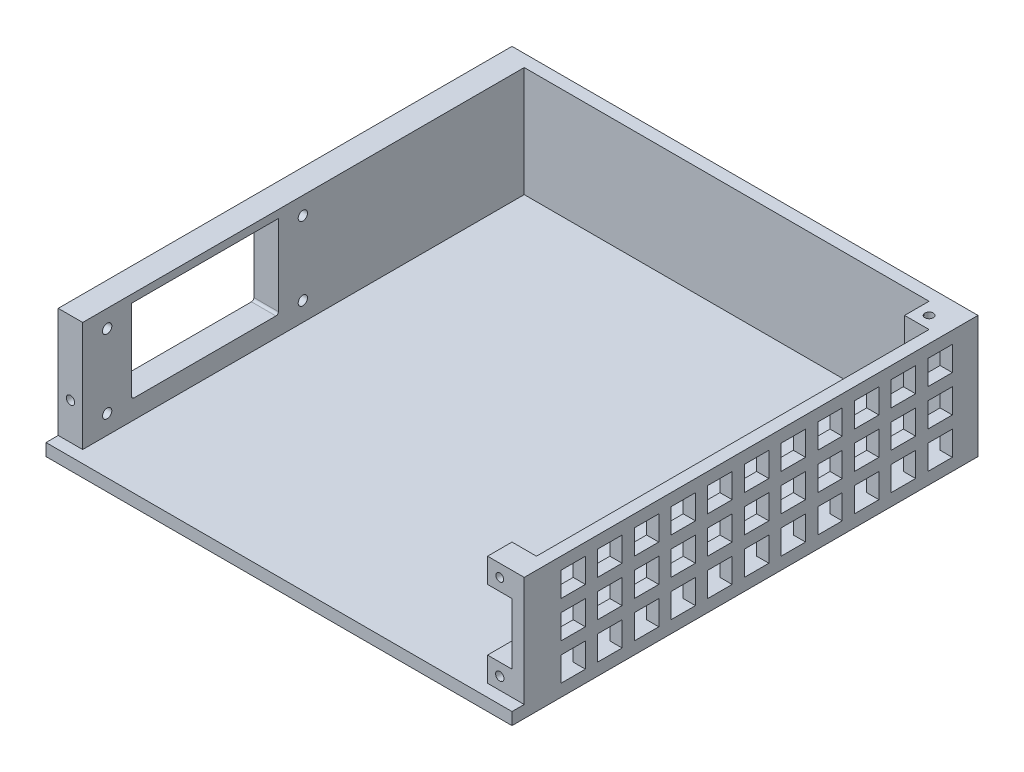
SolidWorks part; units mm, degrees
ref_plane "Front Plane" through (0, 0, 0) normal (0, 0, 1) x (1, 0, 0)
ref_plane "Top Plane" through (0, 0, 0) normal (0, 1, 0) x (1, 0, 0)
ref_plane "Right Plane" through (0, 0, 0) normal (1, 0, 0) x (0, 0, -1)
sketch "Sketch1" plane through (0, 0, 0) normal (0, 1, 0) x (1, 0, 0)
  line L1 (-95.25, 95.25) -> (95.25, 95.25)
  line L2 (-95.25, 95.25) -> (-95.25, -95.25)
  line L3 (-95.25, -95.25) -> (95.25, -95.25)
  line L4 (95.25, 95.25) -> (95.25, -95.25)
  line L5 (-95.25, 95.25) -> (95.25, -95.25) construction
  line L6 (-95.25, -95.25) -> (95.25, 95.25) construction
  point P0 (0, 0)
  dimension "D1" = 190.5
  dimension "D2" = 190.5
extrude "Boss-Extrude1" add sketch "Sketch1" along normal blind 5
sketch "Sketch9" plane through (0, 5, 0) normal (0, 1, 0) x (1, 0, 0)
  line L0 (95.25, -95.25) -> (95.25, 95.25) construction
  line L1 (-95.25, 95.25) -> (95.25, 95.25)
  line L2 (-95.25, 95.25) -> (-95.25, 90.25)
  line L3 (-95.25, 90.25) -> (95.25, 90.25)
  line L4 (95.25, 95.25) -> (95.25, 90.25)
  dimension "D1" = 5
extrude "Boss-Extrude5" add sketch "Sketch9" along normal blind 45
sketch "Sketch10" plane through (0, 5, 0) normal (0, 1, 0) x (1, 0, 0)
  line L0 (-95.25, -95.25) -> (95.25, -95.25) construction
  line L1 (95.25, 90.25) -> (90.25, 90.25)
  line L2 (95.25, 90.25) -> (95.25, -95.25)
  line L3 (95.25, -95.25) -> (90.25, -95.25)
  line L4 (90.25, 90.25) -> (90.25, -95.25)
  dimension "D1" = 5
extrude "Boss-Extrude6" add sketch "Sketch10" along normal up to surface (45 mm away) up to face at (0, 50, -92.75)
sketch "Sketch11" plane through (95.25, 0, 0) normal (1, 0, 0) x (0, 0, -1)
  line L0 (-95.25, 50) -> (95.25, 50) construction
  line L1 (-65.25, 45) -> (-75.25, 45)
  line L2 (-65.25, 45) -> (-65.25, 35)
  line L3 (-65.25, 35) -> (-75.25, 35)
  line L4 (-75.25, 45) -> (-75.25, 35)
  line L5 (-95.25, 50) -> (-95.25, 0) construction
  dimension "D1" = 5
  dimension "D2" = 20
  dimension "D3" = 10
  dimension "D4" = 10
extrude "Cut-Extrude3" cut sketch "Sketch11" against normal up to surface (5 mm away) up to face at (90.25, 27.5, 2.5)
pattern_linear "LPattern3" count 3 spacing 15 along (0, -1, 0) of "Cut-Extrude3"
pattern_linear "LPattern4" count 11 spacing 15 along (0, 0, -1) of "LPattern3"
sketch "Sketch12" plane through (-95.25, 0, 0) normal (-1, 0, 0) x (0, 0, 1)
  line L1 (-90.25, 5) -> (-80.25, 5)
  line L2 (-90.25, 5) -> (-90.25, 15)
  line L3 (-90.25, 15) -> (-80.25, 15)
  line L4 (-80.25, 5) -> (-80.25, 15)
  dimension "D1" = 10
  dimension "D2" = 10
extrude "Boss-Extrude7" add sketch "Sketch12" against normal blind 10
mirror "Mirror1" about plane through (0, 0, 0) normal (0, 0, 1) of "Boss-Extrude7"
sketch "Sketch13" plane through (0, 50, 0) normal (0, 1, 0) x (1, 0, 0)
  line L0 (90.25, 90.25) -> (90.25, -95.25) construction
  line L1 (95.25, -95.25) -> (90.25, -95.25)
  line L2 (95.25, -95.25) -> (95.25, -90.25)
  line L3 (95.25, -90.25) -> (90.25, -90.25)
  line L4 (90.25, -95.25) -> (90.25, -90.25)
  dimension "D1" = 5
extrude "Cut-Extrude4" cut sketch "Sketch13" against normal up to surface (45 mm away) up to face at (65.5463, 5, -0.3426)
sketch "Sketch15" plane through (0, 0, -90.25) normal (0, 0, 1) x (1, 0, 0)
  line L1 (-95.25, 50) -> (-85.25, 50)
  line L2 (-95.25, 50) -> (-95.25, 40)
  line L3 (-95.25, 40) -> (-85.25, 40)
  line L4 (-85.25, 50) -> (-85.25, 40)
  line L5 (90.25, 50) -> (80.25, 50)
  line L6 (90.25, 50) -> (90.25, 40)
  line L7 (90.25, 40) -> (80.25, 40)
  line L8 (80.25, 50) -> (80.25, 40)
  dimension "D1" = 10
  dimension "D2" = 10
extrude "Boss-Extrude8" add sketch "Sketch15" along normal blind 10
sketch "Sketch17" plane through (0, 50, 0) normal (0, 1, 0) x (1, 0, 0)
  line L1 (80.25, 80.25) -> (80.25, 90.25) construction
  line L2 (90.25, 80.25) -> (80.25, 80.25) construction
  circle A0 centre (85.25, 85.25) radius 1.7
  dimension "D1" = 3.4
  dimension "D2" = 5
  dimension "D3" = 5
extrude "Cut-Extrude7" cut sketch "Sketch17" against normal up to surface (10 mm away) up to face at (86.25, 40, -85.15)
sketch "Sketch18" plane through (90.25, 0, 0) normal (-1, 0, 0) x (0, 0, 1)
  line L1 (90.25, 50) -> (80.25, 50)
  line L2 (90.25, 50) -> (90.25, 40)
  line L3 (90.25, 40) -> (80.25, 40)
  line L4 (80.25, 50) -> (80.25, 40)
  dimension "D1" = 10
  dimension "D2" = 10
extrude "Boss-Extrude9" add sketch "Sketch18" along normal blind 10
sketch "Sketch19" plane through (0, 0, 90.25) normal (0, 0, 1) x (1, 0, 0)
  line L0 (80.25, 40) -> (80.25, 50) construction
  line L1 (80.25, 40) -> (90.25, 40) construction
  circle A0 centre (85.25, 45) radius 1.6
  dimension "D1" = 5
  dimension "D2" = 3.2
  dimension "D3" = 5
extrude "Cut-Extrude8" cut sketch "Sketch19" against normal up to surface (10 mm away) up to face at (85.25, 45, 80.25)
sketch "Sketch20" plane through (0, 0, 90.25) normal (0, 0, 1) x (1, 0, 0)
  line L1 (-85.25, 15) -> (-95.25, 15)
  line L2 (-85.25, 15) -> (-85.25, 25)
  line L3 (-85.25, 25) -> (-95.25, 25)
  line L4 (-95.25, 15) -> (-95.25, 25)
  dimension "D1" = 10
  dimension "D2" = 10
extrude "Boss-Extrude10" add sketch "Sketch20" against normal up to surface (10 mm away) up to face at (-90.25, 10, 80.25)
sketch "Sketch22" plane through (90.25, 0, 0) normal (-1, 0, 0) x (0, 0, 1)
  line L1 (90.25, 5) -> (80.25, 5)
  line L2 (90.25, 5) -> (90.25, 15)
  line L3 (90.25, 15) -> (80.25, 15)
  line L4 (80.25, 5) -> (80.25, 15)
  dimension "D1" = 10
  dimension "D2" = 10
extrude "Boss-Extrude11" add sketch "Sketch22" along normal blind 10
sketch "Sketch23" plane through (0, 0, 90.25) normal (0, 0, 1) x (1, 0, 0)
  line L0 (80.25, 5) -> (80.25, 15) construction
  line L1 (80.25, 15) -> (90.25, 15) construction
  circle A0 centre (85.25, 10) radius 1.7
  dimension "D1" = 3.4
  dimension "D2" = 5
  dimension "D3" = 5
extrude "Cut-Extrude10" cut sketch "Sketch23" against normal up to surface (10 mm away) up to face at (85.25, 10, 80.25)
sketch "Sketch24" plane through (-95.25, 0, 0) normal (-1, 0, 0) x (0, 0, 1)
  line L0 (-80.25, 50) -> (-80.25, 40)
  line L1 (-80.25, 50) -> (-80.25, 40) construction
  line L2 (-80.25, 40) -> (-90.25, 40)
  line L3 (-90.25, 40) -> (-90.25, 15)
  line L4 (-90.25, 15) -> (-80.25, 15)
  line L5 (-80.25, 15) -> (-80.25, 5)
  line L6 (-80.25, 5) -> (80.25, 5)
  line L7 (80.25, 5) -> (80.25, 25)
  line L8 (80.25, 25) -> (90.25, 25)
  line L9 (90.25, 25) -> (90.25, 50)
  line L10 (90.25, 50) -> (-80.25, 50)
extrude "Boss-Extrude12" add sketch "Sketch24" against normal up to surface (10 mm away) up to face at (-85.25, 45, -85.25)
sketch "Sketch25" plane through (-95.25, 0, 0) normal (-1, 0, 0) x (0, 0, 1)
  line L3 (10.25, 46.8) -> (10.25, 13.8)
  line L4 (11.25, 12.8) -> (69.25, 12.8)
  line L5 (70.25, 13.8) -> (70.25, 46.8)
  line L6 (0.25, 42.8) -> (80.25, 42.8) construction
  line L7 (80.25, 42.8) -> (80.25, 12.8) construction
  line L8 (80.25, 12.8) -> (0.25, 12.8) construction
  line L9 (0.25, 12.8) -> (0.25, 42.8) construction
  line L10 (10.25, 46.8) -> (70.25, 46.8)
  line L11 (-95.25, 0) -> (95.25, 0) construction
  line L12 (90.25, 50) -> (90.25, 5) construction
  arc A6 (10.25, 13.8) -> (11.25, 12.8) centre (11.25, 13.8) ccw
  arc A7 (69.25, 12.8) -> (70.25, 13.8) centre (69.25, 13.8) ccw
  circle A8 centre (0.25, 42.8) radius 1.9
  circle A9 centre (0.25, 12.8) radius 1.9
  circle A10 centre (80.25, 12.8) radius 1.9
  circle A11 centre (80.25, 42.8) radius 1.9
  point P13 (40.25, 42.8)
  point P15 (40.25, 12.8)
  point P22 (0, 0)
  point P23 (0, 0)
  dimension "D1" = 3.8
  dimension "D6" = 1
  dimension "D2" = 80
  dimension "D3" = 30
  dimension "D4" = 34
  dimension "D5" = 60
  dimension "D7" = 12.8
  dimension "D8" = 20
extrude "Cut-Extrude11" cut sketch "Sketch25" against normal up to next
sketch "Sketch21" plane through (0, 0, 90.25) normal (0, 0, 1) x (1, 0, 0)
  line L1 (-85.25, 50) -> (-85.25, 5) construction
  line L2 (-85.25, 5) -> (-95.25, 5) construction
  circle A0 centre (-90.25, 20) radius 1.7
  dimension "D1" = 3.4
  dimension "D2" = 15
  dimension "D3" = 5
extrude "Cut-Extrude9" cut sketch "Sketch21" against normal up to next
